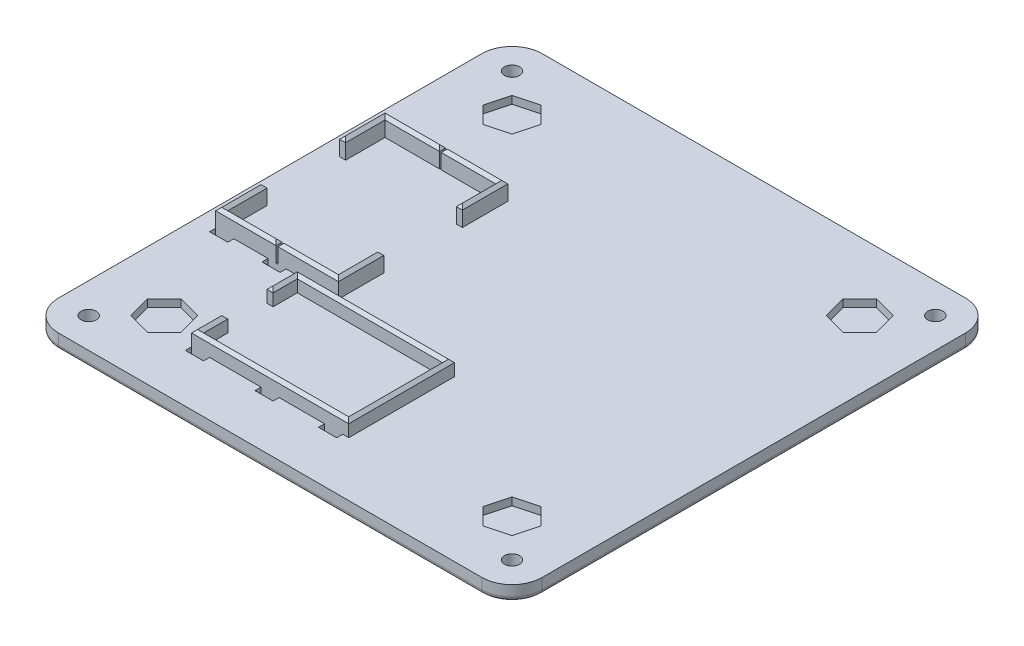
SolidWorks part; units mm, degrees
ref_plane "Front Plane" through (0, 0, 0) normal (0, 0, 1) x (1, 0, 0)
ref_plane "Top Plane" through (0, 0, 0) normal (0, 1, 0) x (1, 0, 0)
ref_plane "Right Plane" through (0, 0, 0) normal (1, 0, 0) x (0, 0, -1)
sketch "Sketch1" plane through (0, 0, 0) normal (0, 1, 0) x (1, 0, 0)
  line L1 (0, 0) -> (203.2, 0)
  line L2 (0, 0) -> (0, 203.2)
  line L3 (0, 203.2) -> (203.2, 203.2)
  line L4 (203.2, 0) -> (203.2, 203.2)
  dimension "D1" = 203.2
  dimension "D2" = 203.2
extrude "Boss-Extrude1" add sketch "Sketch1" along normal blind 6.35
fillet "Fillet1" radius 12.7 4 edges at (0, 3.175, -203.2) (0, 3.175, 0) (203.2, 3.175, 0) (203.2, 3.175, -203.2)
sketch "Sketch2" plane through (0, 0, 0) normal (0, -1, 0) x (1, 0, 0)
  circle A0 centre (12.7, -12.7) radius 3.175
  circle A1 centre (190.5, -12.7) radius 3.175
  circle A2 centre (190.5, -190.5) radius 3.175
  circle A3 centre (12.7, -190.5) radius 3.175
  arc A4 (190.5, -203.2) -> (203.2, -190.5) centre (190.5, -190.5) ccw construction
  arc A5 (12.7, 0) -> (0, -12.7) centre (12.7, -12.7) ccw construction
  dimension "D1" = 6.35
extrude "Cut-Extrude1" cut sketch "Sketch2" against normal through all
sketch "Sketch22" plane through (0, 6.35, 0) normal (0, 1, 0) x (1, 0, 0)
  line L17 (190.5, 203.2) -> (12.7, 203.2) construction
  line L18 (203.2, 12.7) -> (203.2, 190.5) construction
  line L21 (181.6542, 181.6542) -> (172.0521, 184.2271)
  line L22 (172.0521, 184.2271) -> (165.0229, 177.1979)
  line L23 (165.0229, 177.1979) -> (167.5958, 167.5958)
  line L24 (167.5958, 167.5958) -> (177.1979, 165.0229)
  line L25 (177.1979, 165.0229) -> (184.2271, 172.0521)
  line L26 (184.2271, 172.0521) -> (181.6542, 181.6542)
  line L27 (174.625, 174.625) -> (190.5, 190.5) construction
  line L28 (101.6, 203.2) -> (101.6, 0) construction
  line L29 (12.7, 0) -> (190.5, 0) construction
  line L30 (203.2, 101.6) -> (0, 101.6) construction
  line L31 (0, 190.5) -> (0, 12.7) construction
  line L32 (28.575, 174.625) -> (12.7, 190.5) construction
  line L33 (18.9729, 172.0521) -> (21.5458, 181.6542)
  line L34 (26.0021, 165.0229) -> (18.9729, 172.0521)
  line L35 (35.6042, 167.5958) -> (26.0021, 165.0229)
  line L36 (38.1771, 177.1979) -> (35.6042, 167.5958)
  line L37 (31.1479, 184.2271) -> (38.1771, 177.1979)
  line L38 (21.5458, 181.6542) -> (31.1479, 184.2271)
  line L39 (174.625, 28.575) -> (190.5, 12.7) construction
  line L40 (184.2271, 31.1479) -> (181.6542, 21.5458)
  line L41 (177.1979, 38.1771) -> (184.2271, 31.1479)
  line L42 (167.5958, 35.6042) -> (177.1979, 38.1771)
  line L43 (165.0229, 26.0021) -> (167.5958, 35.6042)
  line L44 (172.0521, 18.9729) -> (165.0229, 26.0021)
  line L45 (181.6542, 21.5458) -> (172.0521, 18.9729)
  line L46 (28.575, 28.575) -> (12.7, 12.7) construction
  line L47 (21.5458, 21.5458) -> (31.1479, 18.9729)
  line L48 (31.1479, 18.9729) -> (38.1771, 26.0021)
  line L49 (38.1771, 26.0021) -> (35.6042, 35.6042)
  line L50 (35.6042, 35.6042) -> (26.0021, 38.1771)
  line L51 (26.0021, 38.1771) -> (18.9729, 31.1479)
  line L52 (18.9729, 31.1479) -> (21.5458, 21.5458)
  circle A0 centre (174.625, 174.625) radius 8.609 construction
  circle A1 centre (28.575, 174.625) radius 8.609 construction
  circle A2 centre (174.625, 28.575) radius 8.609 construction
  circle A3 centre (28.575, 28.575) radius 8.609 construction
  dimension "D5" = 17.218
  dimension "D3" = 28.575
  dimension "D4" = 28.575
extrude "Cut-Extrude2" cut sketch "Sketch22" against normal blind 3.175
sketch "Sketch23" plane through (0, 6.35, 0) normal (0, 1, 0) x (1, 0, 0)
  line L1 (59.182, 142.24) -> (33.782, 142.24)
  line L2 (59.182, 142.24) -> (59.182, 123.19)
  line L3 (59.182, 71.12) -> (33.782, 71.12)
  line L4 (7.62, 142.24) -> (7.62, 123.19)
  line L5 (7.62, 142.24) -> (7.62, 203.2) construction
  line L6 (190.5, 203.2) -> (12.7, 203.2) construction
  line L7 (7.62, 71.12) -> (7.62, 0) construction
  line L8 (12.7, 0) -> (190.5, 0) construction
  line L9 (33.02, 142.24) -> (33.02, 139.7)
  line L10 (56.642, 139.7) -> (33.782, 139.7)
  line L11 (56.642, 139.7) -> (56.642, 123.19)
  line L12 (56.642, 73.66) -> (33.782, 73.66)
  line L13 (10.16, 139.7) -> (10.16, 123.19)
  line L14 (33.782, 142.24) -> (33.782, 139.7)
  line L15 (59.182, 123.19) -> (56.642, 123.19)
  line L16 (59.182, 90.17) -> (56.642, 90.17)
  line L17 (10.16, 123.19) -> (7.62, 123.19)
  line L18 (10.16, 90.17) -> (7.62, 90.17)
  line L19 (33.02, 73.66) -> (33.02, 71.12)
  line L20 (33.782, 73.66) -> (33.782, 71.12)
  line L21 (33.02, 142.24) -> (7.62, 142.24)
  line L22 (33.02, 139.7) -> (10.16, 139.7)
  line L23 (59.182, 90.17) -> (59.182, 71.12)
  line L24 (56.642, 90.17) -> (56.642, 73.66)
  line L25 (33.02, 73.66) -> (10.16, 73.66)
  line L26 (33.02, 71.12) -> (7.62, 71.12)
  line L27 (10.16, 90.17) -> (10.16, 73.66)
  line L28 (7.62, 90.17) -> (7.62, 71.12)
  line L29 (0, 190.5) -> (0, 12.7) construction
  point P32 (33.02, 140.97)
  dimension "D2" = 71.12
  dimension "D3" = 51.562
  dimension "D4" = 2.54
  dimension "D5" = 2.54
  dimension "D6" = 2.54
  dimension "D7" = 2.54
  dimension "D8" = 19.05
  dimension "D9" = 19.05
  dimension "D10" = 25.4
  dimension "D11" = 25.4
  dimension "D12" = 19.05
  dimension "D13" = 19.05
  dimension "D14" = 25.4
  dimension "D15" = 25.4
  dimension "D16" = 60.96
  dimension "D17" = 7.62
extrude "Boss-Extrude2" add sketch "Sketch23" along normal blind 7.62
chamfer "Chamfer1" distance 1.27 angle 45 24 edges at (8.89, 13.97, -90.17) (10.16, 13.97, -81.915) (21.59, 13.97, -73.66) (33.02, 13.97, -72.39) (20.32, 13.97, -71.12) (7.62, 13.97, -80.645) (46.482, 13.97, -71.12) (33.782, 13.97, -72.39) (45.212, 13.97, -73.66) (56.642, 13.97, -81.915) (57.912, 13.97, -90.17) (59.182, 13.97, -80.645) (57.912, 13.97, -123.19) (56.642, 13.97, -131.445) (45.212, 13.97, -139.7) (33.782, 13.97, -140.97) (46.482, 13.97, -142.24) (59.182, 13.97, -132.715) (33.02, 13.97, -140.97) (21.59, 13.97, -139.7) (10.16, 13.97, -131.445) (8.89, 13.97, -123.19) (7.62, 13.97, -132.715) (20.32, 13.97, -142.24)
sketch "Sketch24" plane through (0, 6.35, 0) normal (0, 1, 0) x (1, 0, 0)
  line L0 (12.7, 0) -> (190.5, 0) construction
  line L1 (109.22, 64.77) -> (48.26, 64.77)
  line L2 (109.22, 64.77) -> (109.22, 25.4)
  line L3 (109.22, 25.4) -> (48.26, 25.4)
  line L4 (48.26, 64.77) -> (48.26, 54.61)
  line L5 (0, 190.5) -> (0, 12.7) construction
  line L6 (111.76, 67.31) -> (45.72, 67.31)
  line L7 (111.76, 67.31) -> (111.76, 22.86)
  line L8 (111.76, 22.86) -> (45.72, 22.86)
  line L9 (45.72, 67.31) -> (45.72, 54.61)
  line L10 (45.72, 54.61) -> (48.26, 54.61)
  line L11 (45.72, 35.56) -> (48.26, 35.56)
  line L12 (45.72, 35.56) -> (45.72, 22.86)
  line L13 (48.26, 35.56) -> (48.26, 25.4)
  dimension "D1" = 39.37
  dimension "D2" = 60.96
  dimension "D3" = 25.4
  dimension "D4" = 2.54
  dimension "D5" = 2.54
  dimension "D6" = 2.54
  dimension "D7" = 2.54
  dimension "D8" = 48.26
  dimension "D9" = 12.7
  dimension "D10" = 12.7
extrude "Boss-Extrude3" add sketch "Sketch24" along normal blind 6.35
chamfer "Chamfer2" distance 1.27 angle 45 12 edges at (78.74, 12.7, -64.77) (48.26, 12.7, -59.69) (46.99, 12.7, -54.61) (45.72, 12.7, -60.96) (78.74, 12.7, -67.31) (111.76, 12.7, -45.085) (78.74, 12.7, -22.86) (45.72, 12.7, -29.21) (46.99, 12.7, -35.56) (48.26, 12.7, -30.48) (78.74, 12.7, -25.4) (109.22, 12.7, -45.085)
fillet "Fillet2" radius 1.905 12 edges at (3.7197, 0, -3.7197) (101.6, 0, 0) (199.4803, 0, -3.7197) (203.2, 0, -101.6) (199.4803, 0, -199.4803) (101.6, 0, -203.2) (3.7197, 0, -199.4803) (0, 0, -101.6) (12.7, 0, -15.875) (190.5, 0, -15.875) (190.5, 0, -193.675) (12.7, 0, -193.675)
sketch "Sketch25" plane through (0, 6.35, 0) normal (0, 1, 0) x (1, 0, 0)
  line L0 (59.182, 142.24) -> (33.782, 142.24) construction
  line L1 (54.102, 142.24) -> (46.482, 142.24)
  line L2 (54.102, 142.24) -> (54.102, 144.78)
  line L3 (54.102, 144.78) -> (46.482, 144.78)
  line L4 (46.482, 142.24) -> (46.482, 144.78)
  line L5 (33.782, 71.12) -> (59.182, 71.12) construction
  line L6 (56.3959, 71.12) -> (45.72, 71.12)
  line L7 (56.3959, 71.12) -> (56.3959, 67.31)
  line L8 (56.3959, 67.31) -> (45.72, 67.31)
  line L9 (45.72, 71.12) -> (45.72, 67.31)
  line L10 (111.76, 67.31) -> (45.72, 67.31) construction
  line L11 (45.72, 67.31) -> (111.76, 67.31) construction
  line L12 (45.72, 22.86) -> (111.76, 22.86) construction
  line L13 (74.93, 67.31) -> (82.55, 67.31)
  line L14 (74.93, 67.31) -> (74.93, 69.85)
  line L15 (74.93, 69.85) -> (82.55, 69.85)
  line L16 (82.55, 67.31) -> (82.55, 69.85)
  line L17 (109.22, 67.31) -> (101.6, 67.31)
  line L18 (109.22, 67.31) -> (109.22, 69.85)
  line L19 (109.22, 69.85) -> (101.6, 69.85)
  line L20 (101.6, 67.31) -> (101.6, 69.85)
  line L21 (109.22, 22.86) -> (101.6, 22.86)
  line L22 (109.22, 22.86) -> (109.22, 20.32)
  line L23 (109.22, 20.32) -> (101.6, 20.32)
  line L24 (101.6, 22.86) -> (101.6, 20.32)
  line L25 (7.62, 71.12) -> (33.02, 71.12) construction
  line L26 (82.55, 22.86) -> (74.93, 22.86)
  line L27 (82.55, 22.86) -> (82.55, 20.32)
  line L28 (82.55, 20.32) -> (74.93, 20.32)
  line L29 (74.93, 22.86) -> (74.93, 20.32)
  line L30 (45.72, 22.86) -> (53.34, 22.86)
  line L31 (45.72, 22.86) -> (45.72, 20.32)
  line L32 (45.72, 20.32) -> (53.34, 20.32)
  line L33 (53.34, 22.86) -> (53.34, 20.32)
  line L34 (29.591, 71.12) -> (37.211, 71.12)
  line L35 (29.591, 71.12) -> (29.591, 68.58)
  line L36 (29.591, 68.58) -> (37.211, 68.58)
  line L37 (37.211, 71.12) -> (37.211, 68.58)
  line L38 (33.02, 142.24) -> (7.62, 142.24) construction
  line L39 (7.62, 71.12) -> (15.24, 71.12)
  line L40 (7.62, 71.12) -> (7.62, 68.58)
  line L41 (7.62, 68.58) -> (15.24, 68.58)
  line L42 (15.24, 71.12) -> (15.24, 68.58)
  line L43 (7.62, 142.24) -> (15.24, 142.24)
  line L44 (7.62, 142.24) -> (7.62, 144.78)
  line L45 (7.62, 144.78) -> (15.24, 144.78)
  line L46 (15.24, 142.24) -> (15.24, 144.78)
  line L47 (29.591, 142.24) -> (37.211, 142.24)
  line L48 (29.591, 142.24) -> (29.591, 144.78)
  line L49 (29.591, 144.78) -> (37.211, 144.78)
  line L50 (37.211, 142.24) -> (37.211, 144.78)
  line L51 (33.782, 139.7) -> (33.02, 139.7) construction
  line L53 (109.22, 25.4) -> (109.22, 64.77) construction
  point P65 (33.401, 142.24)
  point P66 (33.401, 139.7)
  point P67 (33.401, 71.12)
  point P68 (78.74, 69.85)
  point P69 (78.74, 67.31)
  point P70 (78.74, 20.32)
  dimension "D1" = 7.62
  dimension "D2" = 2.54
extrude "Cut-Extrude3" cut sketch "Sketch25" against normal through all
fillet "Fillet5" radius 2.54 44 edges at (50.292, 0, -142.24) (46.482, 0, -143.51) (50.292, 0, -144.78) (54.102, 0, -143.51) (11.43, 0, -71.12) (15.24, 0, -69.85) (11.43, 0, -68.58) (7.62, 0, -69.85) (33.401, 0, -71.12) (37.211, 0, -69.85) (33.401, 0, -68.58) (29.591, 0, -69.85) (49.53, 0, -22.86) (53.34, 0, -21.59) (49.53, 0, -20.32) (45.72, 0, -21.59) (78.74, 0, -20.32) (74.93, 0, -21.59) (78.74, 0, -22.86) (82.55, 0, -21.59) (105.41, 0, -20.32) (101.6, 0, -21.59) (105.41, 0, -22.86) (109.22, 0, -21.59) (105.41, 0, -67.31) (101.6, 0, -68.58) (105.41, 0, -69.85) (109.22, 0, -68.58) (78.74, 0, -69.85) (82.55, 0, -68.58) (78.74, 0, -67.31) (74.93, 0, -68.58) (51.0579, 0, -67.31) (45.72, 0, -69.215) (51.0579, 0, -71.12) (56.3959, 0, -69.215) (11.43, 0, -144.78) (15.24, 0, -143.51) (11.43, 0, -142.24) (7.62, 0, -143.51) (33.401, 0, -144.78) (37.211, 0, -143.51) (33.401, 0, -142.24) (29.591, 0, -143.51)
